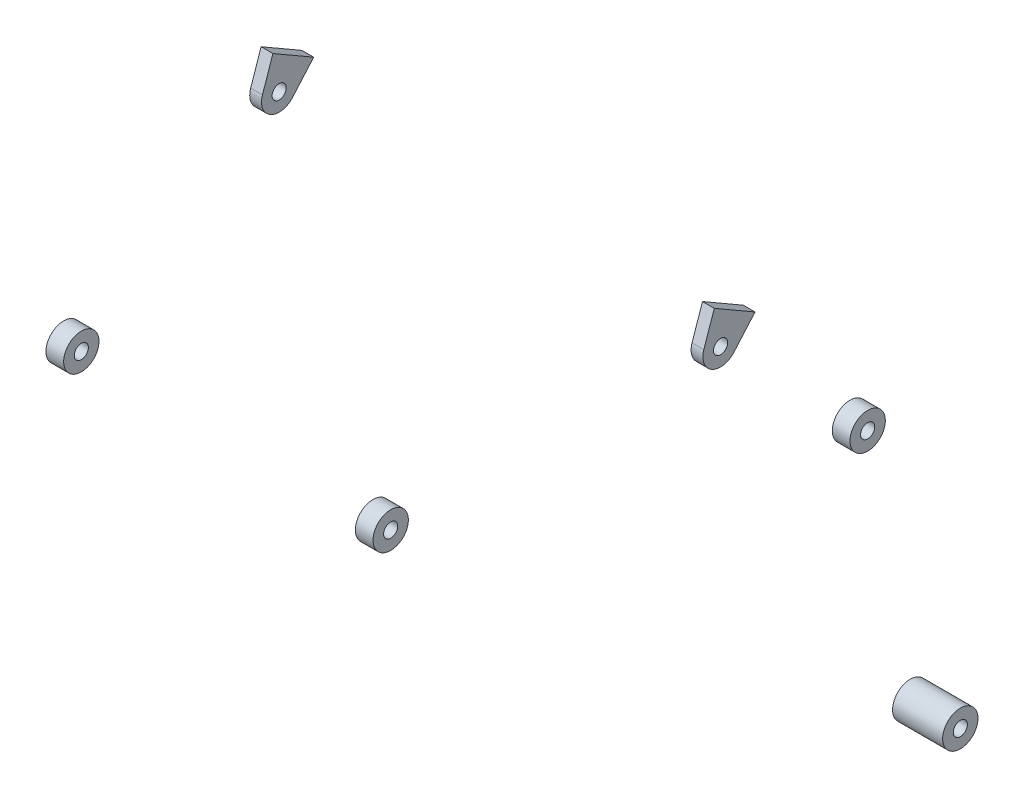
SolidWorks part; units mm, degrees
ref_plane "Front" through (0, 0, 0) normal (0, 0, 1) x (1, 0, 0)
ref_plane "Top" through (0, 0, 0) normal (0, 1, 0) x (1, 0, 0)
ref_plane "Right" through (0, 0, 0) normal (1, 0, 0) x (0, 0, -1)
sketch "Sketch1" plane through (0, 0, 0) normal (1, 0, 0) x (0, 0, -1)
  line L0 (0, 0) -> (-226.3851, -48.3945)
  dimension "D1" = 231.5
sketch "Sketch2" plane through (0, 0, 0) normal (1, 0, 0) x (0, 0, -1)
  line L0 (-5.3205, 30.7846) -> (29.3205, 10.7846)
  line L1 (-14.1922, 4.856) -> (-5.3205, 30.7846)
  line L3 (11.3015, -9.8628) -> (29.3205, 10.7846)
  line L4 (0, 0) -> (53.6021, 0) construction
  circle A0 centre (0, 0) radius 6
  arc A1 (-14.1922, 4.856) -> (11.3015, -9.8628) centre (0, 0) ccw
  dimension "D2" = 30
  dimension "D3" = 12
  dimension "D1" = 150
  dimension "D4" = 40
  dimension "D5" = 24
extrude "Boss-Extrude1" add sketch "Sketch2" along normal blind 10
ref_plane "Plane1" through (-43.5, 0, 0) normal (1, 0, 0) x (0, 0, -1)
sketch "Sketch3" plane through (-43.5, 0, 0) normal (1, 0, 0) x (0, 0, -1)
  circle A0 centre (-226.3851, -48.3945) radius 6
  circle A1 centre (-226.3851, -48.3945) radius 15
  dimension "D1" = 12
  dimension "D2" = 30
extrude "Boss-Extrude2" add sketch "Sketch3" against normal blind 15 separate body
sketch "Sketch4" plane through (-43.5, 0, 0) normal (1, 0, 0) x (0, 0, -1)
  line L0 (-226.3851, -48.3945) -> (243.4571, -422.3577)
  line L1 (0, 0) -> (-226.3851, -48.3945) construction
  dimension "D1" = 600.5
  dimension "D2" = 50.584
ref_plane "Plane2" through (-72.5, 0, 0) normal (1, 0, 0) x (0, 0, -1)
sketch "Sketch5" plane through (-72.5, 0, 0) normal (1, 0, 0) x (0, 0, -1)
  circle A0 centre (243.4571, -422.3577) radius 6
  circle A1 centre (243.4571, -422.3577) radius 15
  dimension "D1" = 12
  dimension "D2" = 30
extrude "Boss-Extrude3" add sketch "Sketch5" along normal blind 42.5 separate body
sketch "Sketch6" plane through (-30, 0, 0) normal (1, 0, 0) x (0, 0, -1)
  line L0 (243.4571, -422.3577) -> (0, 0)
ref_plane "Plane3" through (-79.5, 0, 0) normal (1, 0, 0) x (0, 0, -1)
sketch "Sketch7" plane through (-79.5, 0, 0) normal (1, 0, 0) x (0, 0, -1)
  line L0 (-226.3851, -48.3945) -> (199.3407, -198.76)
  line L1 (199.3407, -198.76) -> (0, 0)
  line L2 (199.3407, -198.76) -> (243.4571, -422.3577)
  circle A1 centre (199.3407, -198.76) radius 6
  circle A2 centre (199.3407, -198.76) radius 15
  point P3 (199.3407, -198.76)
  dimension "D3" = 12
  dimension "D4" = 30
  dimension "D1" = 451.5
  dimension "D2" = 281.5
extrude "Boss-Extrude4" add sketch "Sketch7" along normal blind 15 separate body contours L0 A2 L2 A1 | L2 A2 L1 A1 | L1 A2 L0 A1 region at (-79.5, -192.8735, -189.9875) region at (-79.5, -204.7757, -192.3847) region at (-79.5, -185.2603, -204.9209)
ref_plane "Plane4" through (-182.25, 0, 0) normal (-1, 0, 0) x (0, 0, 1)
mirror "Mirror5" about plane through (-182.25, 0, 0) normal (-1, 0, 0) of bodies 102 101
